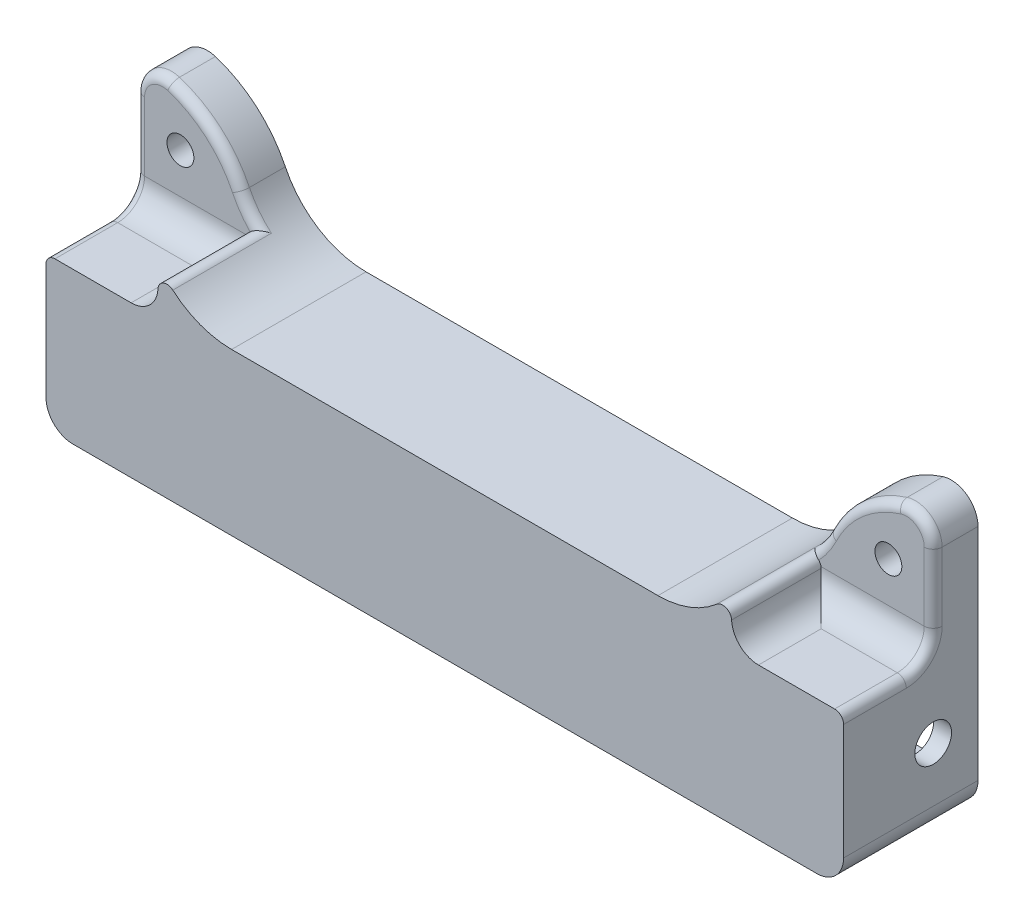
SolidWorks part; units mm, degrees
material "ABS"
ref_plane "Plano frontal" through (0, 0, 0) normal (0, 0, 1) x (1, 0, 0)
ref_plane "Plano superior" through (0, 0, 0) normal (0, 1, 0) x (1, 0, 0)
ref_plane "Plano direito" through (0, 0, 0) normal (1, 0, 0) x (0, 0, -1)
sketch "Esboço1" plane through (0, 0, 0) normal (0, 0, 1) x (1, 0, 0)
  line L0 (33.4361, 75.3989) -> (-49.5639, 75.3989)
  line L11 (10.9361, 93.3989) -> (-27.0639, 93.3989) construction
  line L13 (10.9361, 93.3989) -> (-27.0639, 93.3989)
  line L14 (-52.5639, 78.3989) -> (-52.5639, 93.3989)
  line L15 (-52.5639, 102.9383) -> (-52.5639, 93.3989)
  line L16 (36.4361, 102.9383) -> (36.4361, 93.3989)
  line L18 (15.7238, 93.3989) -> (10.9361, 93.3989)
  line L19 (36.4361, 78.3989) -> (36.4361, 93.3989)
  line L20 (-31.8516, 93.3989) -> (-27.0639, 93.3989)
  arc A0 (-49.5639, 75.3989) -> (-52.5639, 78.3989) centre (-49.5639, 78.3989) cw
  arc A1 (33.4361, 75.3989) -> (36.4361, 78.3989) centre (33.4361, 78.3989) ccw
  arc A6 (36.4361, 102.9383) -> (32.5361, 105.8001) centre (33.4361, 102.9383) ccw
  arc A7 (-40.8569, 99.0511) -> (-48.6639, 105.8001) centre (-52.5639, 93.3989) ccw
  arc A8 (-40.8569, 99.0511) -> (-31.8516, 93.3989) centre (-31.8516, 103.3989) ccw
  arc A9 (-52.5639, 102.9383) -> (-48.6639, 105.8001) centre (-49.5639, 102.9383) cw
  arc A10 (24.7292, 99.0511) -> (15.7238, 93.3989) centre (15.7238, 103.3989) cw
  arc A11 (24.7292, 99.0511) -> (32.5361, 105.8001) centre (36.4361, 93.3989) cw
  point P45 (36.4361, 106.3989)
  point P46 (-52.5639, 106.3989)
  dimension "D1" = 3
extrude "Ressalto-extrusão3" add sketch "Esboço1" along normal blind 15
sketch "Esboço2" plane through (0, 0, 0) normal (0, 0, -1) x (-1, 0, 0)
  line L0 (15.5639, 89.5989) -> (15.5639, 79.3989)
  line L1 (-36.4361, 78.3989) -> (-36.4361, 102.9383) construction
  line L2 (-33.4361, 90.5989) -> (-0.4361, 90.5989)
  line L3 (-34.4361, 89.5989) -> (-34.4361, 79.3989)
  line L4 (-33.4361, 78.3989) -> (-0.4361, 78.3989)
  line L5 (49.5639, 78.3989) -> (16.5639, 78.3989)
  line L6 (50.5639, 89.5989) -> (50.5639, 79.3989)
  line L7 (49.5639, 90.5989) -> (16.5639, 90.5989)
  line L8 (0.5639, 89.5989) -> (0.5639, 79.3989)
  line L9 (49.5639, 75.3989) -> (-33.4361, 75.3989) construction
  line L10 (8.0639, 93.3989) -> (8.0639, 75.3989) construction
  line L11 (-15.7238, 93.3989) -> (31.8516, 93.3989) construction
  line L12 (52.5639, 102.9383) -> (52.5639, 78.3989) construction
  arc A0 (-34.4361, 79.3989) -> (-33.4361, 78.3989) centre (-34.4361, 78.3989) ccw
  arc A1 (-33.4361, 90.5989) -> (-34.4361, 89.5989) centre (-34.4361, 90.5989) ccw
  arc A2 (-0.4361, 78.3989) -> (0.5639, 79.3989) centre (0.5639, 78.3989) ccw
  arc A3 (0.5639, 89.5989) -> (-0.4361, 90.5989) centre (0.5639, 90.5989) ccw
  arc A4 (15.5639, 89.5989) -> (16.5639, 90.5989) centre (15.5639, 90.5989) cw
  arc A5 (16.5639, 78.3989) -> (15.5639, 79.3989) centre (15.5639, 78.3989) cw
  arc A6 (49.5639, 90.5989) -> (50.5639, 89.5989) centre (50.5639, 90.5989) cw
  arc A7 (50.5639, 79.3989) -> (49.5639, 78.3989) centre (50.5639, 78.3989) cw
  dimension "D5" = 2
  dimension "D6" = 2
  dimension "D7" = 2
  dimension "D8" = 2
  dimension "D1" = 2
  dimension "D2" = 3
  dimension "D3" = 12.2
  dimension "D4" = 35
extrude "Corte-extrusão1" cut sketch "Esboço2" against normal blind 10.1
sketch "Esboço3" plane through (0, 0, 0) normal (0, 0, -1) x (-1, 0, 0)
  line L0 (-36.4361, 78.3989) -> (-36.4361, 102.9383) construction
  line L1 (52.5639, 102.9383) -> (52.5639, 78.3989) construction
  circle A0 centre (-31.4361, 99.8001) radius 1.5
  circle A1 centre (47.5639, 99.8001) radius 1.5
  dimension "D1" = 5
  dimension "D2" = 3
  dimension "D3" = 6
  dimension "D4" = 5
  dimension "D5" = 6
  dimension "D6" = 3
extrude "Corte-extrusão2" cut sketch "Esboço3" against normal through all
sketch "Esboço4" plane through (34.4361, 0, 0) normal (-1, 0, 0) x (0, 0, 1)
  line L0 (0, 89.5989) -> (0, 79.3989) construction
  line L1 (0, 79.3989) -> (10, 79.3989) construction
  line L2 (0, 79.3989) -> (0, 89.5989) construction
  line L3 (0, 89.5989) -> (10, 89.5989) construction
  line L4 (10, 79.3989) -> (10, 89.5989) construction
  line L5 (10.1, 89.5989) -> (0, 89.5989) construction
  circle A0 centre (5, 84.4989) radius 2.05
  dimension "D1" = 4.1
  dimension "D2" = 5
  dimension "D3" = 5.1
extrude "Corte-extrusão3" cut sketch "Esboço4" against normal through all
sketch "Esboço5" plane through (-50.5639, 0, 0) normal (1, 0, 0) x (0, 0, -1)
  line L0 (-10.1, 79.3989) -> (0, 79.3989) construction
  line L1 (0, 89.5989) -> (-10, 89.5989) construction
  line L2 (0, 89.5989) -> (0, 79.3989) construction
  line L3 (0, 79.3989) -> (-10, 79.3989) construction
  line L4 (-10, 89.5989) -> (-10, 79.3989) construction
  circle A0 centre (-5, 84.4989) radius 2.05
  dimension "D3" = 5
  dimension "D4" = 5.1
  dimension "D5" = 4.1
  dimension "D6" = 5
  dimension "D1" = 10.2
  dimension "D2" = 10
extrude "Corte-extrusão4" cut sketch "Esboço5" against normal through all
sketch "Esboço6" plane through (0, 0, 15) normal (0, 0, 1) x (1, 0, 0)
  line L1 (-55.0639, 107.3001) -> (-40.0639, 107.3001)
  line L2 (-55.0639, 107.3001) -> (-55.0639, 92.3001)
  line L3 (-55.0639, 92.3001) -> (-40.0639, 92.3001)
  line L4 (-40.0639, 107.3001) -> (-40.0639, 92.3001)
  line L5 (-55.0639, 107.3001) -> (-40.0639, 92.3001) construction
  line L6 (-55.0639, 92.3001) -> (-40.0639, 107.3001) construction
  line L7 (23.9361, 107.3001) -> (38.9361, 107.3001)
  line L8 (23.9361, 107.3001) -> (23.9361, 92.3001)
  line L9 (23.9361, 92.3001) -> (38.9361, 92.3001)
  line L10 (38.9361, 107.3001) -> (38.9361, 92.3001)
  line L11 (23.9361, 107.3001) -> (38.9361, 92.3001) construction
  line L12 (23.9361, 92.3001) -> (38.9361, 107.3001) construction
  point P0 (-47.5639, 99.8001)
  point P6 (31.4361, 99.8001)
  dimension "D1" = 15
extrude "Corte-extrusão5" cut sketch "Esboço6" against normal blind 10
fillet "Filete1" radius 3 4 edges at (-40.0639, 92.3001, 10) (-46.3139, 92.3001, 5) (30.1861, 92.3001, 5) (23.9361, 92.3001, 10)
fillet "Filete2" radius 1 14 edges at (-40.4871, 98.3564, 5) (-44.062, 103.2335, 5) (-51.3387, 105.357, 5) (-52.5639, 92.3001, 11.5) (-52.5639, 93.1788, 5.8787) (-40.0639, 97.693, 10) (-52.5639, 99.1192, 5) (36.4361, 92.3001, 11.5) (36.4361, 93.1788, 5.8787) (36.4361, 99.1192, 5) (35.2109, 105.357, 5) (24.3594, 98.3564, 5) (27.9343, 103.2335, 5) (23.9361, 97.693, 10)
